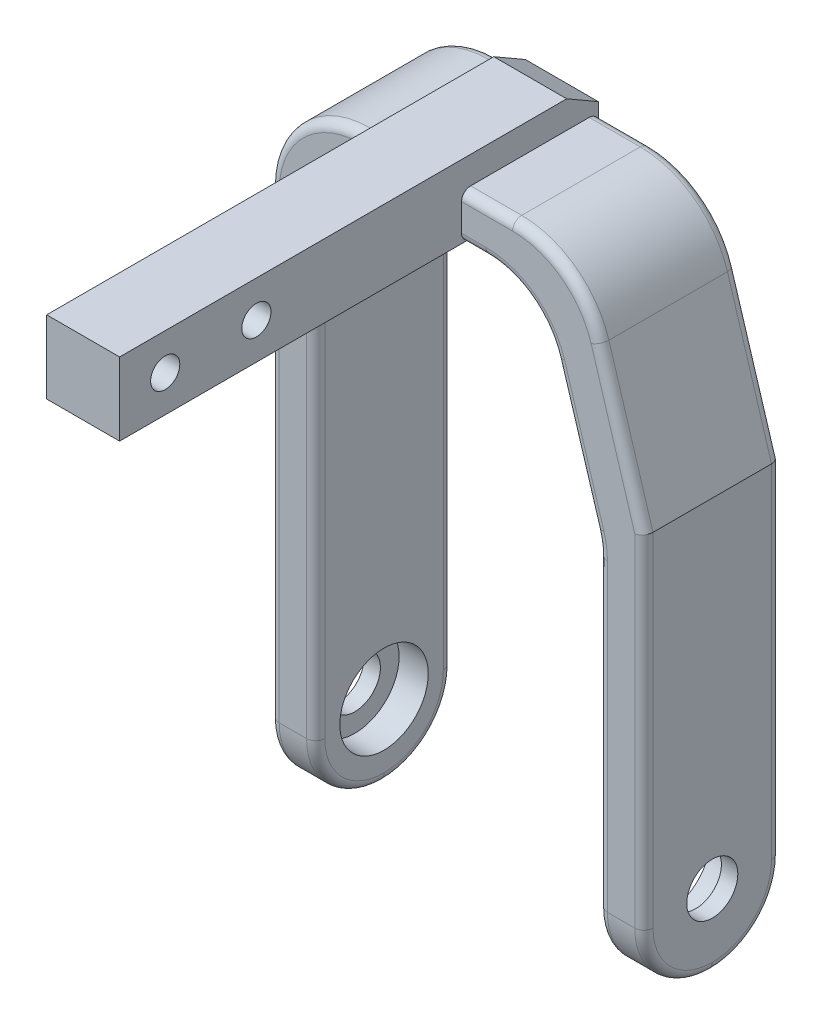
SolidWorks part; units mm, degrees
ref_plane "前视基准面" through (0, 0, 0) normal (0, 0, 1) x (1, 0, 0)
ref_plane "上视基准面" through (0, 0, 0) normal (0, 1, 0) x (1, 0, 0)
ref_plane "右视基准面" through (0, 0, 0) normal (1, 0, 0) x (0, 0, -1)
sketch "草图1" plane through (0, 0, 0) normal (0, 1, 0) x (1, 0, 0)
  line L1 (24, 7.5) -> (-17, 7.5)
  line L2 (24, 7.5) -> (24, -7.5)
  line L3 (24, -7.5) -> (-17, -7.5)
  line L4 (-17, 7.5) -> (-17, -7.5)
  line L5 (24, 7.5) -> (-17, -7.5) construction
  line L6 (24, -7.5) -> (-17, 7.5) construction
  point P0 (0, 0)
extrude "凸台-拉伸1" add sketch "草图1" against normal blind 68
sketch "草图3" plane through (0, 0, 7.5) normal (0, 0, 1) x (1, 0, 0)
  line L0 (-17, -68) -> (24, -68) construction
  line L1 (-12, -68) -> (19, -68)
  line L2 (-12, -68) -> (-12, -5)
  line L3 (-12, -5) -> (12.6087, -5)
  line L4 (19, -68) -> (19, -25.9143)
  line L5 (12.6087, -5) -> (19, -25.9143)
  line L6 (17, 0) -> (27.4891, -34.3238)
  line L7 (17, 0) -> (27.4891, 0)
  line L8 (27.4891, 0) -> (27.4891, -34.3238)
  line L9 (-17, 0) -> (24, 0) construction
  line L10 (-17, 0) -> (24, 0) construction
extrude "切除-拉伸1" cut sketch "草图3" against normal through all
fillet "圆角1" radius 8 3 edges at (-12, -5, 0) (19, -25.9143, 0) (12.6087, -5, 0)
fillet "圆角3" radius 7.5 4 edges at (21.5, -68, -7.5) (21.5, -68, 7.5) (-14.5, -68, -7.5) (-14.5, -68, 7.5)
sketch "草图4" plane through (24, 0, 0) normal (1, 0, 0) x (0, 0, -1)
  circle A0 centre (0, -60) radius 2.8
extrude "切除-拉伸2" cut sketch "草图4" against normal through all
sketch "草图6" plane through (19, 0, 0) normal (1, 0, 0) x (0, 0, -1)
  circle A0 centre (0, -60) radius 4.85
extrude "切除-拉伸4" cut sketch "草图6" along normal blind 3.2
ref_plane "基准面1" through (3.5, 0, 0) normal (1, 0, 0) x (0, 0, -1)
mirror "镜向2" about plane through (3.5, 0, 0) normal (1, 0, 0) of "切除-拉伸4"
sketch "草图7" plane through (0, 0, 0) normal (1, 0, 0) x (0, 0, -1)
  line L1 (-45, -5) -> (7.5, -5)
  line L2 (-45, -5) -> (-45, 3)
  line L3 (-45, 3) -> (7.5, 3)
  line L4 (7.5, -5) -> (7.5, 3)
  circle A2 centre (-30, -1) radius 1.6
  circle A3 centre (-40, -1) radius 1.6
  point P4 (0, 0)
  point P5 (0, 0)
extrude "凸台-拉伸2" add sketch "草图7" along normal mid plane 8
chamfer "倒角1" distance 2 angle 60 1 edges at (0, 3, -7.5) first distance on face at (4.7083, -20.0893, -7.5)
fillet "圆角4" radius 10 2 edges at (17, 0, 0) (-17, 0, 0)
fillet "圆角2" radius 1 36 edges at (-17, -35.25, -7.5) (24, -41.7031, -7.5) (24, -41.7031, 7.5) (-17, -35.25, 7.5) (-9.6569, -7.3431, 7.5) (5.3441, -5, 7.5) (19, -43.8047, 7.5) (19, -43.8047, -7.5) (1.3441, -5, -7.5) (-9.6569, -7.3431, -7.5) (-12, -36.75, -7.5) (-12, -36.75, 7.5) (19, -65.8033, 5.3033) (19, -65.8033, -5.3033) (-12, -65.8033, -5.3033) (-12, -65.8033, 5.3033) (-17, -65.8033, 5.3033) (-17, -65.8033, -5.3033) (24, -65.8033, -5.3033) (24, -65.8033, 5.3033) (11.4473, -6.5694, 7.5) (16.4949, -17.7167, 7.5) (18.9122, -25.9274, 7.5) (18.9122, -25.9274, -7.5) (16.4949, -17.7167, -7.5) (11.4473, -6.5694, -7.5) (21.5814, -14.9919, -7.5) (21.5814, -14.9919, 7.5) (6.7997, 0, -7.5) (15.5481, -1.9618, -7.5) (6.7997, 0, 7.5) (15.5481, -1.9618, 7.5) (-5.5, 0, -7.5) (-14.0711, -2.9289, -7.5) (-5.5, 0, 7.5) (-14.0711, -2.9289, 7.5)
